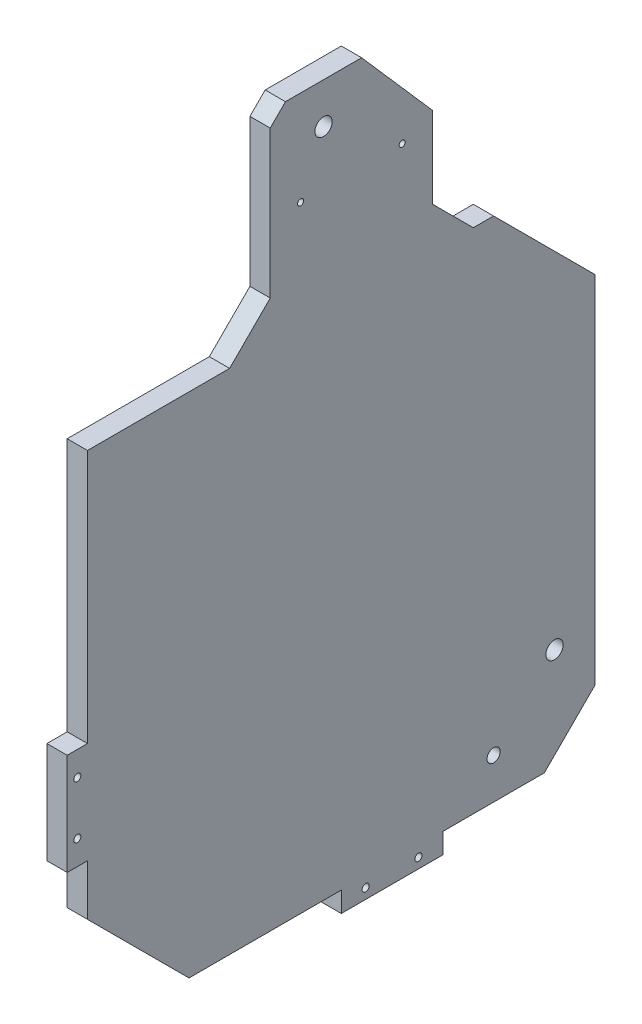
SolidWorks part; units mm, degrees
material "ABS PC"
ref_plane "Спереди" through (0, 0, 0) normal (0, 0, 1) x (1, 0, 0)
ref_plane "Сверху" through (0, 0, 0) normal (0, 1, 0) x (1, 0, 0)
ref_plane "Справа" through (0, 0, 0) normal (1, 0, 0) x (0, 0, -1)
sketch "Sketch1" plane through (0, 0, 0) normal (1, 0, 0) x (0, 0, -1)
  line L0 (50, 0) -> (125, 0)
  line L1 (0, 250) -> (70, 250)
  line L2 (200, 250) -> (250, 200)
  line L3 (250, 200) -> (250, 25)
  line L4 (125, 0) -> (125, -10)
  line L5 (125, -10) -> (175, -10)
  line L6 (175, -10) -> (175, 0)
  line L7 (175, 0) -> (225, 0)
  line L8 (0, 250) -> (0, 125)
  line L9 (0, 125) -> (-10, 125)
  line L10 (-10, 125) -> (-10, 75)
  line L11 (-10, 75) -> (0, 75)
  line L12 (0, 75) -> (0, 50)
  line L13 (90, 270) -> (90, 342.5)
  line L14 (200, 250) -> (250, 250) construction
  line L15 (250, 250) -> (250, 200) construction
  line L16 (250, 25) -> (250, 0) construction
  line L17 (250, 25) -> (225, 0)
  line L18 (0, 50) -> (50, 0)
  line L19 (250, 0) -> (225, 0) construction
  line L20 (0, 50) -> (0, 0) construction
  line L21 (0, 0) -> (50, 0) construction
  line L22 (97.5, 350) -> (135, 350)
  line L23 (170, 310) -> (170, 270)
  line L24 (190, 250) -> (200, 250)
  line L25 (90, 342.5) -> (97.5, 350)
  line L26 (135, 350) -> (170, 310)
  line L27 (70, 250) -> (90, 270)
  line L28 (170, 270) -> (190, 250)
  circle A0 centre (-5, 113) radius 1.75
  circle A1 centre (-5, 87) radius 1.75
  circle A2 centre (137, -5) radius 1.75
  circle A3 centre (163, -5) radius 1.75
  point P26 (90, 250)
  point P27 (90, 350)
  point P38 (170, 250)
  dimension "D13" = 3.5
  dimension "D16" = 5
  dimension "D17" = 12
  dimension "D18" = 12
  dimension "D19" = 5
  dimension "D1" = 250
  dimension "D2" = 250
  dimension "D3" = 50
  dimension "D4" = 50
  dimension "D5" = 50
  dimension "D6" = 50
  dimension "D7" = 50
  dimension "D8" = 25
  dimension "D9" = 25
  dimension "D10" = 10
  dimension "D11" = 75
  dimension "D12" = 75
  dimension "D14" = 12
  dimension "D15" = 12
  dimension "D20" = 100
  dimension "D21" = 35
  dimension "D22" = 90
  dimension "D29" = 7.5
  dimension "D23" = 80
  dimension "D31" = 20
  dimension "D33" = 20
  dimension "D24" = 40
extrude "Boss-Extrude1" add sketch "Sketch1" along normal blind 10
sketch "Sketch2" plane through (0, 225, -225) normal (0, 0.7071, -0.7071) x (1, 0, 0)
  line L1 (10, 35.3553) -> (10, -35.3553) construction
  line L2 (10, -35.3553) -> (0, -35.3553) construction
  circle A0 centre (5, 4.6447) radius 1.5
  circle A1 centre (5, -25.3553) radius 1.5
  dimension "D1" = 3
  dimension "D2" = 30
  dimension "D3" = 10
  dimension "D4" = 5
extrude "Cut-Extrude1" cut sketch "Sketch2" against normal blind 15
sketch "Sketch3" plane through (10, 0, 0) normal (1, 0, 0) x (0, 0, -1)
  line L0 (175, 0) -> (225, 0) construction
  line L1 (250, 25) -> (250, 200) construction
  line L2 (135, 350) -> (97.5, 350) construction
  circle A0 centre (230, 50) radius 4.25
  circle A1 centre (200, 20) radius 3.25
  circle A2 centre (116.25, 330) radius 4.25
  point P10 (116.25, 350)
  dimension "D1" = 8.5
  dimension "D3" = 30
  dimension "D4" = 20
  dimension "D5" = 20
  dimension "D6" = 6.5
  dimension "D7" = 8.5
  dimension "D2" = 30
  dimension "D8" = 20
extrude "Cut-Extrude2" cut sketch "Sketch3" against normal through all
sketch "Sketch4" plane through (10, 0, 0) normal (1, 0, 0) x (0, 0, -1)
  line L0 (90, 342.5) -> (90, 270) construction
  line L2 (125, 0) -> (125, -10) construction
  circle A0 centre (105, 303.3321) radius 1.5
  circle A1 centre (155, 303.3321) radius 1.5
  dimension "D2" = 50
  dimension "D3" = 3
  dimension "D4" = 20
  dimension "D1" = 15
extrude "Cut-Extrude3" cut sketch "Sketch4" against normal blind 10
